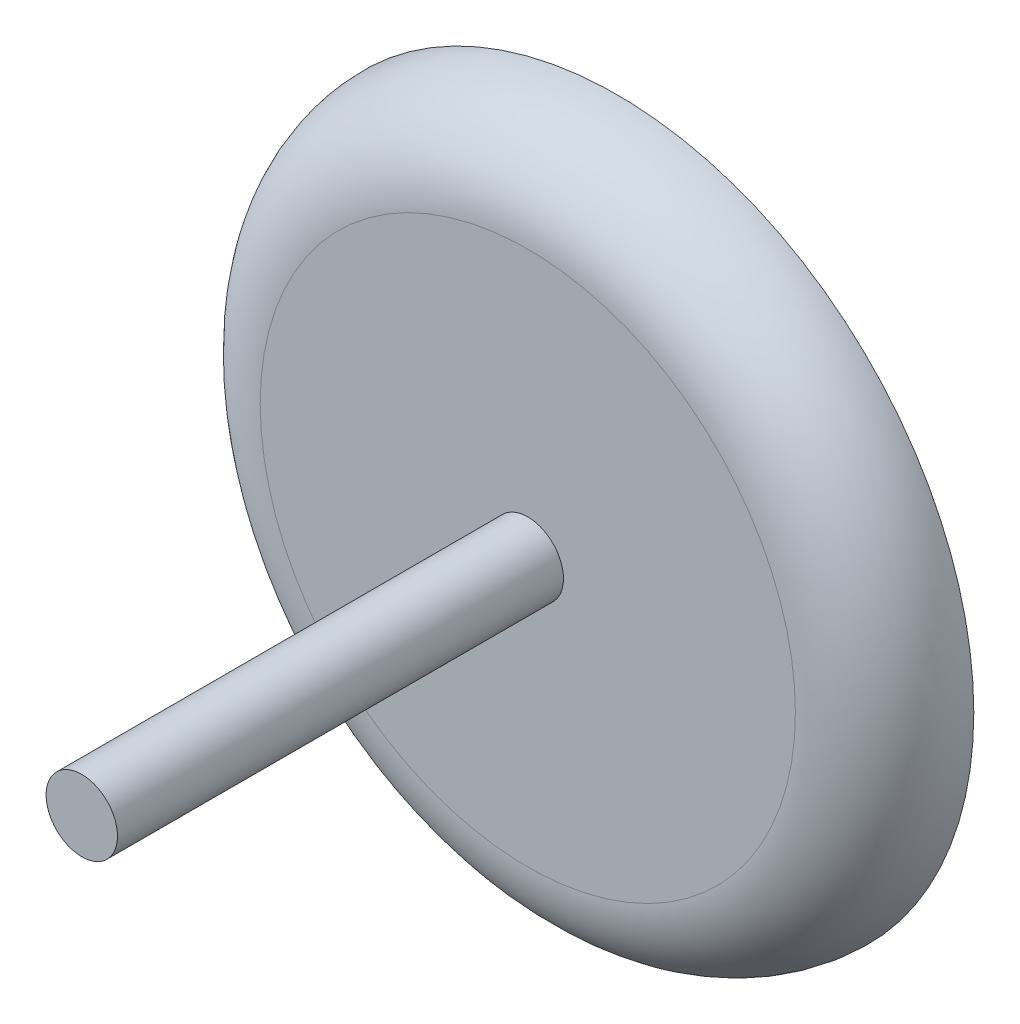
SolidWorks part; units mm, degrees
ref_plane "Plan de face" through (0, 0, 0) normal (0, 0, 1) x (1, 0, 0)
ref_plane "Plan de dessus" through (0, 0, 0) normal (0, 1, 0) x (1, 0, 0)
ref_plane "Plan de droite" through (0, 0, 0) normal (1, 0, 0) x (0, 0, -1)
sketch "Esquisse1" plane through (0, 0, 0) normal (0, 0, 1) x (1, 0, 0)
  circle A0 centre (0, 0) radius 40
  dimension "D1" = 80
extrude "Boss.-Extru.1" add sketch "Esquisse1" along normal blind 10
fillet "Congé1" radius 10 1 edges at (40, 0, 10)
sketch "Esquisse2" plane through (0, 0, 10) normal (0, 0, 1) x (1, 0, 0)
  circle A0 centre (0, 0) radius 4
  dimension "D1" = 8
extrude "Boss.-Extru.2" add sketch "Esquisse2" along normal blind 50
